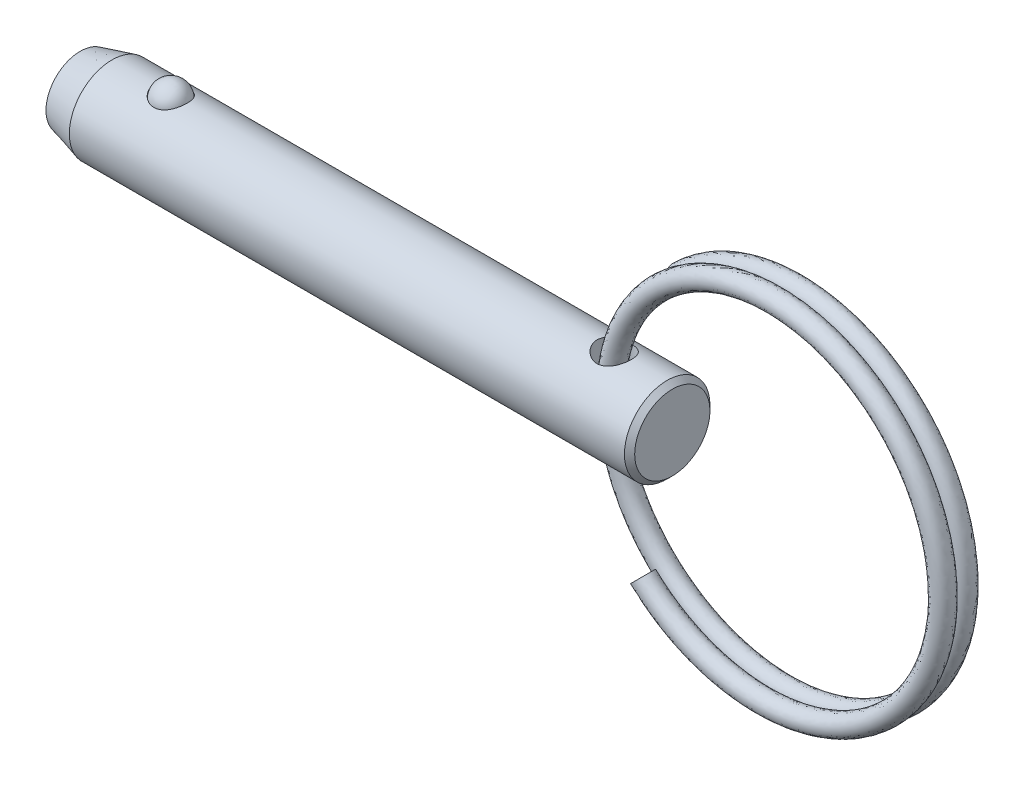
SolidWorks part; units mm, degrees
ref_plane "Front" through (0, 0, 0) normal (0, 0, 1) x (1, 0, 0)
ref_plane "Top" through (0, 0, 0) normal (0, 1, 0) x (1, 0, 0)
ref_plane "Right" through (0, 0, 0) normal (1, 0, 0) x (0, 0, -1)
sketch "Sketch1" plane through (0, 0, 0) normal (0, 0, 1) x (1, 0, 0)
  line L0 (21.9964, 2.794) -> (21.6154, 3.175)
  line L1 (21.6154, 3.175) -> (21.9964, 3.175) construction
  line L4 (21.9964, 2.794) -> (21.9964, 0)
  line L5 (21.9964, 3.175) -> (21.9964, 2.794) construction
  line L16 (21.6154, 3.175) -> (-19.6265, 3.175)
  line L17 (-21.9964, 3.175) -> (-21.9964, 2.54) construction
  line L19 (-19.6265, 3.175) -> (-21.9964, 3.175) construction
  line L22 (-21.9964, -3.175) -> (-19.6265, -3.175) construction
  line L23 (-15.2619, 2.8575) -> (-15.2619, -2.8575) construction
  line L24 (-21.9964, 0) -> (21.9964, 0)
  line L27 (21.9964, 0) -> (24.7904, 0) construction
  line L29 (-21.9964, 0) -> (-21.9964, -2.54) construction
  line L36 (16.4084, 0) -> (16.4084, 3.175) construction
  line L37 (-21.9964, 2.54) -> (-21.9964, 0)
  line L38 (-19.6265, -3.175) -> (21.9964, -3.175) construction
  line L39 (-21.9964, -2.54) -> (-21.9964, -3.175) construction
  line L40 (-19.6265, 3.175) -> (-21.9964, 2.54)
  line L42 (-19.6265, -3.175) -> (-21.9964, -2.54) construction
  line L43 (-19.6265, 3.175) -> (-19.6265, -3.175) construction
  circle A2 centre (-15.2619, 2.8575) radius 1.2319 construction
  point P35 (-14.0716, 3.175)
  dimension "A1" = 15
revolve "Revolve1" add sketch "Sketch1" angle 360 about L27
sketch "Sketch2" plane through (0, 0, 0) normal (0, 0, 1) x (1, 0, 0)
  line L0 (-14.0046, 2.8575) -> (-16.5192, 2.8575)
  line L1 (-15.2619, 4.0894) -> (-15.2619, 4.1148) construction
  line L2 (-14.0046, 2.8575) -> (-11.49, 2.8575) construction
  circle A0 centre (-15.2619, 2.8575) radius 1.2319 construction
  circle A1 centre (-15.2619, 2.8575) radius 1.2319 construction
  arc A2 (-16.5192, 2.8575) -> (-14.0046, 2.8575) centre (-15.2619, 2.8575) cw
  dimension "D1" = 0.0254
revolve "Cut-Revolve1" cut sketch "Sketch2" angle 360 about L2
sketch "Sketch3" plane through (0, 0, 0) normal (0, 0, 1) x (1, 0, 0)
  line L0 (-14.03, 2.8575) -> (-16.4938, 2.8575)
  line L1 (-14.03, 2.8575) -> (-11.5662, 2.8575) construction
  circle A0 centre (-15.2619, 2.8575) radius 1.2319 construction
  arc A1 (-14.03, 2.8575) -> (-16.4938, 2.8575) centre (-15.2619, 2.8575) ccw
revolve "Revolve2" add sketch "Sketch3" angle 360 about L1
sketch "Sketch4" plane through (0, 0, 0) normal (0, 0, 1) x (1, 0, 0)
  line L1 (17.6784, -3.175) -> (18.9484, -3.175)
  line L2 (17.6784, -3.175) -> (17.6784, 3.175)
  line L3 (17.6784, 3.175) -> (18.9484, 3.175)
  line L4 (18.9484, -3.175) -> (18.9484, 3.175)
  line L5 (17.6784, -3.175) -> (17.6784, -4.445) construction
  line L6 (18.9484, 3.175) -> (21.9964, 3.175) construction
  line L8 (16.4084, -3.175) -> (16.4084, 3.175) construction
  line L9 (16.4084, 0) -> (17.6784, 0) construction
  line L11 (17.6784, 0) -> (18.9484, 0) construction
  line L12 (21.6154, 3.175) -> (-19.6265, 3.175) construction
  line L14 (-19.6265, -3.175) -> (21.9964, -3.175) construction
  dimension "D1" = 2.54
revolve "Cut-Revolve2" cut sketch "Sketch4" angle 360 about L2
sketch "Sketch5" plane through (0, 0, 0) normal (0, 0, 1) x (1, 0, 0)
  line L0 (0, 0) -> (16.7014, 0) construction
  line L1 (16.7014, 0) -> (16.7014, 3.175) construction
  line L2 (21.6154, 3.175) -> (-19.6265, 3.175) construction
  line L3 (30.1634, 0) -> (43.6254, 0) construction
  line L4 (18.9484, 3.175) -> (18.6554, 3.175) construction
  line L5 (17.6784, 3.175) -> (18.9484, 3.175) construction
  line L6 (17.0812, 3.175) -> (17.0812, -3.175) construction
  line L7 (16.7014, 3.175) -> (16.4084, 3.175) construction
  line L8 (17.6784, -3.175) -> (18.9484, -3.175) construction
  line L9 (17.0812, -3.175) -> (18.9484, -3.175) construction
  line L10 (16.7014, 0) -> (30.1634, 0) construction
  line L12 (18.6554, 3.175) -> (17.0812, 3.175) construction
  line L13 (30.1634, 11.938) -> (30.1634, 13.462) construction
  circle A0 centre (30.1634, 0) radius 13.462
  circle A1 centre (30.1634, 0) radius 11.938 construction
  circle A2 centre (30.1634, 0) radius 12.7 construction
  point P26 (30.1634, 12.7)
curve "Helix/Spiral1" pitch 1.5494 height 1.3557 radius 13.462 left hand yes centre (30.1634, 0, 0) axis (0, 0, -1) start towards (1, 0, 0)
sketch "Sketch6" plane through (114.0038, 0, 0) normal (0, 1, 0) x (0, 0, -1)
  line L0 (0, 95.7784) -> (0, 96.5404) construction
  line L1 (0, 96.5404) -> (0, 97.3024) construction
  circle A0 centre (0, 96.5404) radius 0.762
  dimension "D1" = 1.524
sketch "Sketch7" plane through (0, 0, 0) normal (0, 0, 1) x (1, 0, 0)
  circle A0 centre (30.1634, 0) radius 13.462 construction
  circle A1 centre (30.1634, 0) radius 13.462
curve "Helix/Spiral2" pitch 1.5494 height 1.3557 radius 13.462 left hand yes centre (30.1634, 0, 0) axis (0, 0, 1) start towards (1, 0, 0)
sweep "Sweep1" add profiles "Sketch6" path "Helix/Spiral1"
sweep "Sweep2" add profiles "Sketch6<2>" path "Helix/Spiral2"
sketch "Sketch6<2>" plane through (114.0038, 0, 0) normal (0, 1, 0) x (0, 0, -1) same geometry as "Sketch6"
equation "\"D12@Sketch1\"=\"A@Sketch1\" * 0.80"
equation "\"D2@Sketch1\"=\"A@Sketch1\" * 0.9"
equation "\"D1@Sketch4\" = \"A@Sketch1\" / 2.5"
equation "\"Ring OD@Sketch5\" = \"R Ring Dia@Sketch5\" * 0.06"
equation "\"D4@Helix/Spiral1\"=\"Ring OD@Sketch5\" + 0.001"
equation "\"D1@Sketch6\"=\"Ring OD@Sketch5\""
equation "\"D4@Helix/Spiral2\" = \"D4@Helix/Spiral1\""
equation "\"D5@Helix/Spiral2\" = \"D5@Helix/Spiral1\""
